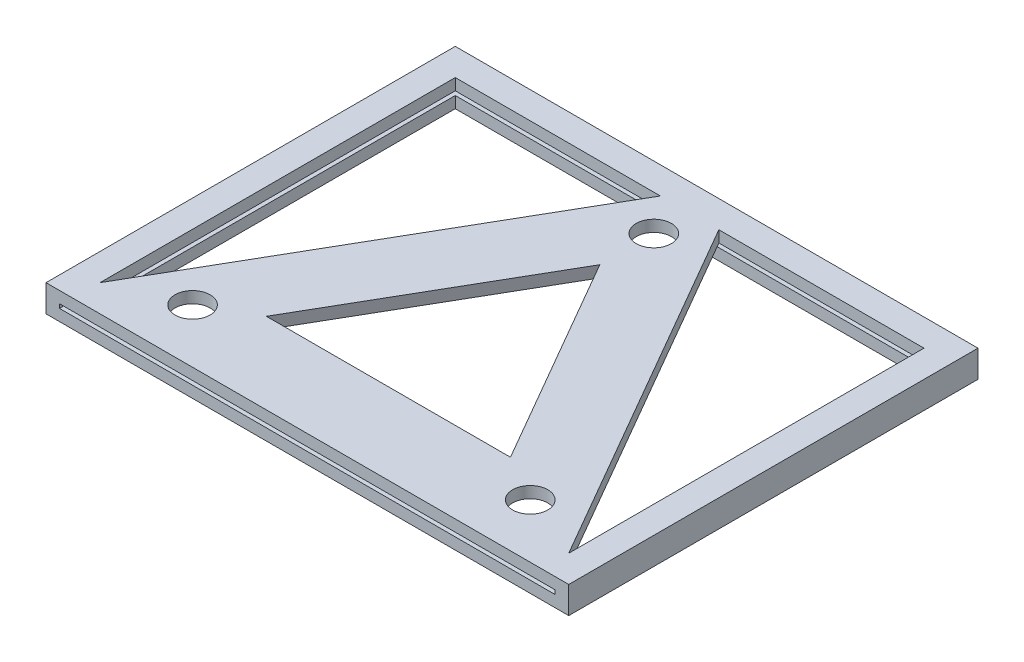
SolidWorks part; units mm, degrees
ref_plane "Front Plane" through (0, 0, 0) normal (0, 0, 1) x (1, 0, 0)
ref_plane "Top Plane" through (0, 0, 0) normal (0, 1, 0) x (1, 0, 0)
ref_plane "Right Plane" through (0, 0, 0) normal (1, 0, 0) x (0, 0, -1)
sketch "Sketch1" plane through (0, 0, 0) normal (0, 1, 0) x (1, 0, 0)
  line L0 (-62.5, -36.0844) -> (0, 72.1688) construction
  line L1 (0, 72.1688) -> (62.5, -36.0844) construction
  line L2 (62.5, -36.0844) -> (-62.5, -36.0844) construction
  line L17 (0, 90.4156) -> (0, 0) construction
  line L18 (0, -36.0844) -> (0, -72.7216) construction
  line L38 (0, 90.4156) -> (0, 95.4156) construction
  line L39 (-91.75, 90.4156) -> (91.75, 90.4156) construction
  line L40 (-91.75, 90.4156) -> (-91.75, -51.0844) construction
  line L41 (-91.75, -51.0844) -> (91.75, -51.0844) construction
  line L42 (91.75, 90.4156) -> (91.75, -51.0844) construction
  line L43 (-96.75, 95.4156) -> (96.75, 95.4156)
  line L44 (-96.75, 95.4156) -> (-96.75, -56.0844)
  line L45 (-96.75, -56.0844) -> (96.75, -56.0844)
  line L46 (96.75, 95.4156) -> (96.75, -56.0844)
  line L48 (91.75, 19.6656) -> (96.75, 19.6656) construction
  line L49 (-10.8284, 85.4156) -> (-86.75, -46.0844)
  line L50 (-86.75, -46.0844) -> (-86.75, 85.4156)
  line L53 (86.75, -46.0844) -> (86.75, 85.4156)
  line L54 (10.8284, 85.4156) -> (86.75, -46.0844)
  line L55 (0, 52.1688) -> (-45.1795, -26.0844)
  line L56 (-45.1795, -26.0844) -> (45.1795, -26.0844)
  line L57 (45.1795, -26.0844) -> (0, 52.1688)
  line L59 (-86.75, 85.4156) -> (86.75, 85.4156)
  line L60 (-86.75, -46.0844) -> (86.75, -46.0844)
  circle A0 centre (0, 0) radius 36.0844 construction
  circle A4 centre (0, 72.1688) radius 6.5
  circle A5 centre (62.5, -36.0844) radius 6.5
  circle A6 centre (-62.5, -36.0844) radius 6.5
  point P10 (0, 0)
  dimension "D2" = 125
  dimension "D5" = 5
  dimension "D7" = 13
  dimension "D3" = 15
  dimension "D8" = 5
  dimension "D9" = 5
  dimension "D10" = 5
  dimension "D11" = 10
  dimension "D12" = 10
  dimension "D6" = 5
  dimension "D4" = 141.5
  dimension "183" = 183.5
extrude "Boss-Extrude1" add sketch "Sketch1" along normal blind 5 contours L42 L39 L40 L41 A6 A5 A4 region at (0, 0, -83.2386)
extrude "Boss-Extrude2" add sketch "Sketch1<8>" along normal mid plane 10 contours L46 L43 L44 L45 L39 L42 L41 L40 region at (0, 0, -92.9581)
sketch "Sketch1<8>" plane through (0, 0, 0) normal (0, 1, 0) x (1, 0, 0) same geometry as "Sketch1"
sketch "Sketch2" plane through (0, 0, 0) normal (0, 1, 0) x (1, 0, 0)
  line L1 (-91.75, -56.0844) -> (91.75, -56.0844)
  line L2 (-91.75, -56.0844) -> (-91.75, 90.4156)
  line L3 (-91.75, 90.4156) -> (91.75, 90.4156)
  line L4 (91.75, -56.0844) -> (91.75, 90.4156)
  line L5 (-91.75, -56.0844) -> (91.75, 90.4156) construction
  line L6 (-91.75, 90.4156) -> (91.75, -56.0844) construction
  line L8 (-96.75, -56.0844) -> (96.75, -56.0844) construction
  line L9 (-96.75, -56.0844) -> (96.75, -56.0844) construction
  line L10 (91.75, 90.4156) -> (91.75, -51.0844) construction
  line L11 (-91.75, 90.4156) -> (91.75, 90.4156) construction
  line L12 (-91.75, 90.4156) -> (-91.75, -51.0844) construction
  point P0 (0, 17.1656)
  point P5 (79.8798, -56.0844)
  point P9 (91.5, -56.0844)
extrude "Cut-Extrude2" cut sketch "Sketch2" against normal mid plane 1.5 contours L2 L1 L4 L3
